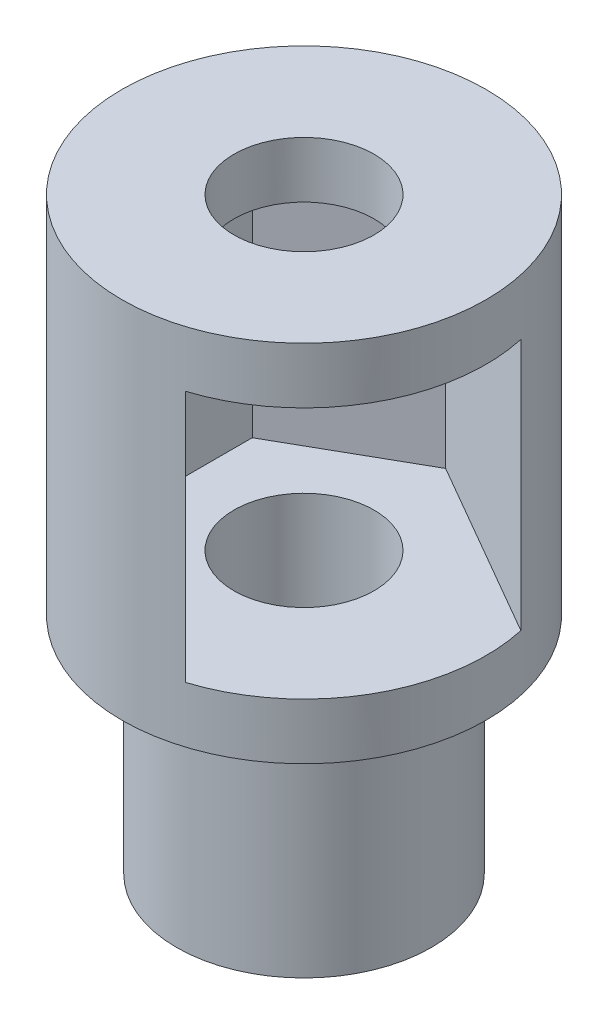
SolidWorks part; units mm, degrees
ref_plane "Front Plane" through (0, 0, 0) normal (0, 0, 1) x (1, 0, 0)
ref_plane "Top Plane" through (0, 0, 0) normal (0, 1, 0) x (1, 0, 0)
ref_plane "Right Plane" through (0, 0, 0) normal (1, 0, 0) x (0, 0, -1)
sketch "Sketch1" plane through (0, 0, 0) normal (0, 1, 0) x (1, 0, 0)
  circle A0 centre (0, 0) radius 4.55
  dimension "D1" = 9.1
extrude "Boss-Extrude1" add sketch "Sketch1" along normal blind 8 contours A0
sketch "Sketch2" plane through (0, 8, 0) normal (0, 1, 0) x (1, 0, 0)
  circle A0 centre (0, 0) radius 2.5
extrude "Cut-Extrude1" cut sketch "Sketch2" against normal blind 8
sketch "Sketch3" plane through (0, 8, 0) normal (0, 1, 0) x (1, 0, 0)
  circle A0 centre (0, 0) radius 6.5
  dimension "D1" = 13
extrude "Boss-Extrude4" add sketch "Sketch3" along normal blind 11 contours A0
sketch "Sketch5" plane through (0, 19, 0) normal (0, 1, 0) x (1, 0, 0)
  line L0 (0, 0) -> (4.3938, 0) construction
  line L3 (4.3938, 2.521) -> (4.3938, -2.521) construction
  line L5 (4.3938, -2.521) -> (-0.0062, -5.0614) construction
  line L9 (-0.0062, -5.0614) -> (-4.4062, -2.521) construction
  line L12 (-4.4062, -2.521) -> (-4.4062, 2.5597)
  line L13 (-4.4062, 2.5597) -> (-0.0062, 5.0614)
  line L14 (-0.0062, 5.0614) -> (4.3938, 2.521) construction
  line L15 (-4.1854, -2.6484) -> (43297.0847, -25002.6484) construction
  line L16 (0.0916, 5.0049) -> (43301.3618, -24994.9951) construction
  line L17 (7.8193, 0.5434) -> (3.436, -7.0487)
  line L18 (-0.0062, 5.0614) -> (7.8193, 0.5434)
  line L19 (3.436, -7.0487) -> (-4.4062, -2.521)
  circle A0 centre (0, 0) radius 6.5 construction
  point P6 (4.3938, 0)
  dimension "D1" = 120
extrude "Cut-Extrude2" cut sketch "Sketch5" against normal blind 9
sketch "Sketch6" plane through (0, 19, 0) normal (0, 1, 0) x (1, 0, 0)
  circle A0 centre (0, 0) radius 6.5
  dimension "D1" = 13
extrude "Boss-Extrude5" add sketch "Sketch6" along normal blind 2
sketch "Sketch7" plane through (0, 0, 0) normal (0, -1, 0) x (1, 0, 0)
  circle A0 centre (0, 0) radius 2.5
extrude "Cut-Extrude3" cut sketch "Sketch7" against normal through all
ref_plane "Plane1" through (6.3492, 19, -1.3921) normal (0, -1, 0) x (-1, 0, 0)
